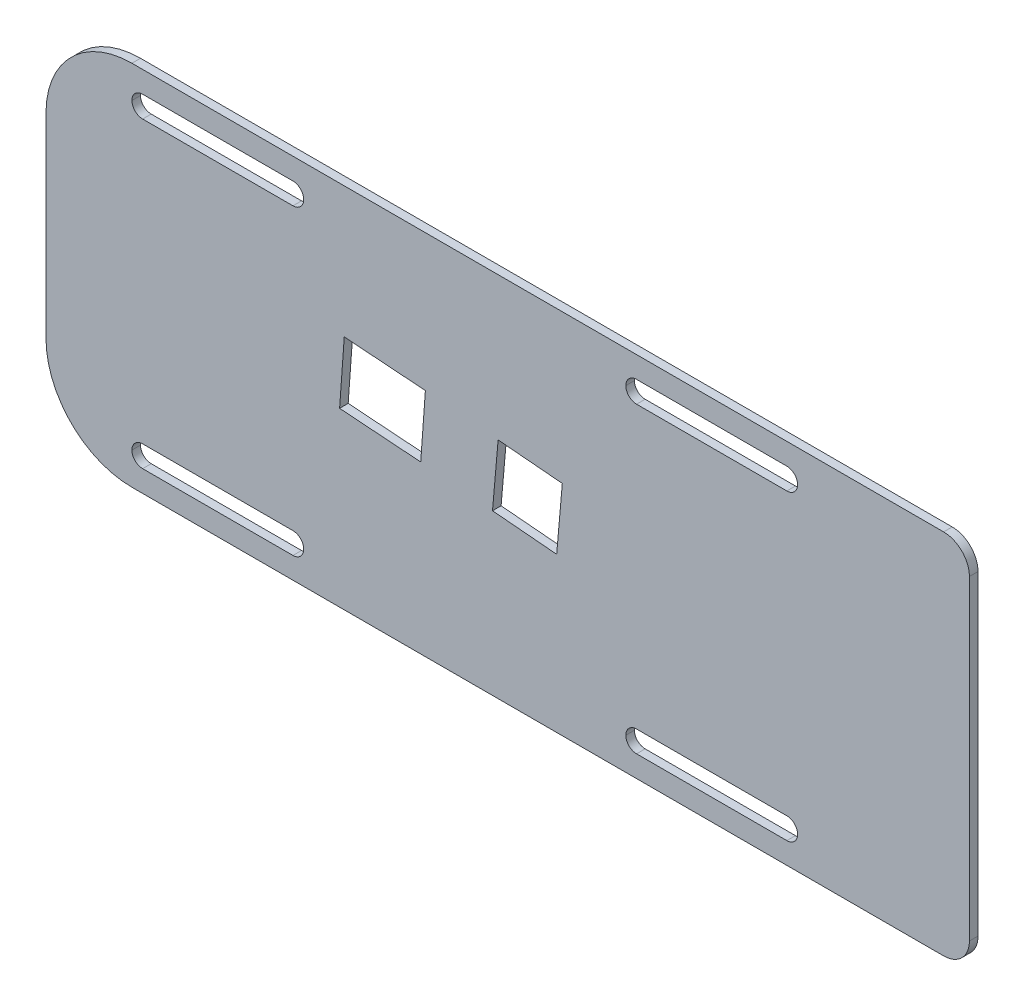
SolidWorks part; units mm, degrees
ref_plane "Plan de face" through (0, 0, 0) normal (0, 0, 1) x (1, 0, 0)
ref_plane "Plan de dessus" through (0, 0, 0) normal (0, 1, 0) x (1, 0, 0)
ref_plane "Plan de droite" through (0, 0, 0) normal (1, 0, 0) x (0, 0, -1)
sketch "Esquisse1" plane through (0, 0, 0) normal (0, 0, 1) x (1, 0, 0)
  line L1 (0, 0) -> (215, 0)
  line L2 (0, 0) -> (0, 85.5)
  line L3 (0, 85.5) -> (215, 85.5)
  line L4 (215, 0) -> (215, 85.5)
  line L5 (175, 5) -> (135, 5)
  line L6 (175, 5) -> (175, 10)
  line L7 (175, 10) -> (135, 10)
  line L8 (135, 5) -> (135, 10)
  line L9 (175, 75.5) -> (135, 75.5)
  line L10 (175, 75.5) -> (175, 80.5)
  line L11 (175, 80.5) -> (135, 80.5)
  line L12 (135, 75.5) -> (135, 80.5)
  line L13 (60, 5) -> (20, 5)
  line L14 (60, 5) -> (60, 10)
  line L15 (60, 10) -> (20, 10)
  line L16 (20, 5) -> (20, 10)
  line L17 (60, 75.5) -> (20, 75.5)
  line L18 (60, 75.5) -> (60, 80.5)
  line L19 (60, 80.5) -> (20, 80.5)
  line L20 (20, 75.5) -> (20, 80.5)
  dimension "D1" = 215
  dimension "D2" = 85.5
  dimension "D3" = 5
  dimension "D4" = 5
  dimension "D5" = 5
  dimension "D6" = 5
  dimension "D7" = 40
  dimension "D8" = 40
  dimension "D9" = 40
  dimension "D10" = 40
  dimension "D11" = 5
  dimension "D12" = 5
  dimension "D13" = 20
  dimension "D14" = 20
  dimension "D15" = 40
  dimension "D16" = 40
  dimension "D17" = 5
  dimension "D18" = 5
extrude "Boss.-Extru.1" add sketch "Esquisse1" along normal blind 2
fillet "Congé1" radius 6 2 edges at (215, 0, 1) (215, 85.5, 1)
fillet "Congé2" radius 20 2 edges at (0, 0, 1) (0, 85.5, 1)
fillet "Congé3" radius 2.5 16 edges at (20, 80.5, 1) (20, 75.5, 1) (60, 75.5, 1) (60, 80.5, 1) (60, 10, 1) (60, 5, 1) (20, 5, 1) (20, 10, 1) (135, 10, 1) (135, 5, 1) (175, 10, 1) (175, 5, 1) (135, 80.5, 1) (135, 75.5, 1) (175, 75.5, 1) (175, 80.5, 1)
sketch "Esquisse2" plane through (0, 0, 0) normal (0, 0, -1) x (-1, 0, 0)
  line L0 (-87.247, 38.7212) -> (-88.3324, 53.6641)
  line L1 (-87.247, 38.7212) -> (-68.3587, 40.0932)
  line L2 (-88.3324, 53.6641) -> (-69.4441, 55.0361)
  line L3 (-68.3587, 40.0932) -> (-69.4441, 55.0361)
  line L4 (-118.9033, 35.9322) -> (-120.2106, 50.8751)
  line L5 (-118.9033, 35.9322) -> (-103.9604, 37.2395)
  line L6 (-120.2106, 50.8751) -> (-105.2677, 52.1825)
  line L7 (-103.9604, 37.2395) -> (-105.2677, 52.1825)
  dimension "D1" = 15
extrude "Enlèv. mat.-Extru.1" cut sketch "Esquisse2" against normal up to next
